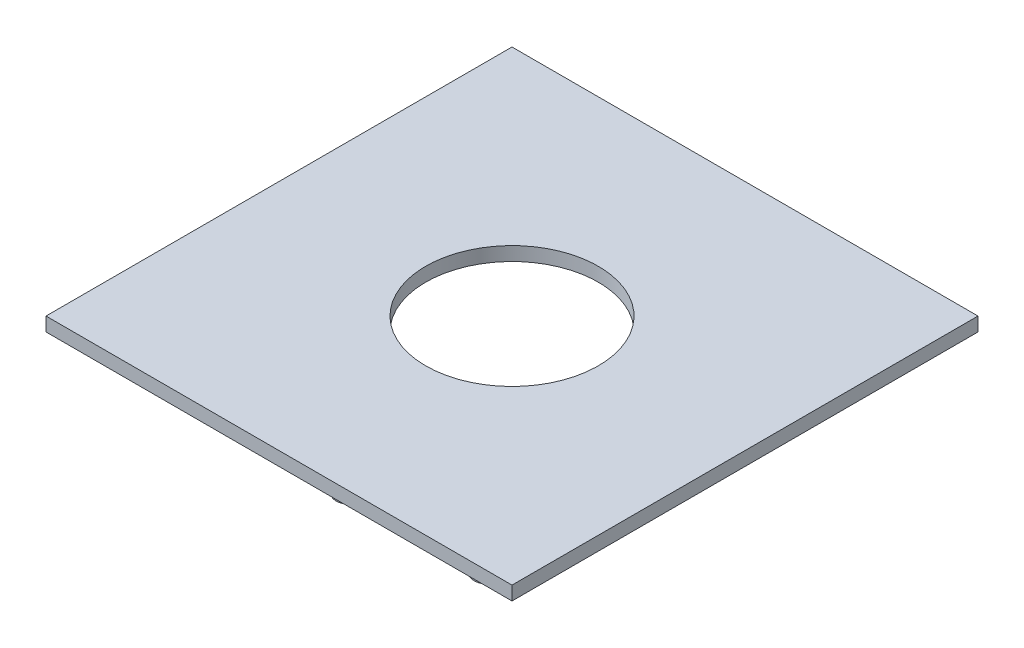
SolidWorks part; units mm, degrees
ref_plane "Front Plane" through (0, 0, 0) normal (0, 0, 1) x (1, 0, 0)
ref_plane "Top Plane" through (0, 0, 0) normal (0, 1, 0) x (1, 0, 0)
ref_plane "Right Plane" through (0, 0, 0) normal (1, 0, 0) x (0, 0, -1)
sketch "Sketch1" plane through (0, 0, 0) normal (0, 1, 0) x (1, 0, 0)
  line L1 (-67.5, 67.5) -> (67.5, 67.5)
  line L2 (-67.5, 67.5) -> (-67.5, -67.5)
  line L3 (-67.5, -67.5) -> (67.5, -67.5)
  line L4 (67.5, 67.5) -> (67.5, -67.5)
  line L5 (-67.5, 67.5) -> (67.5, -67.5) construction
  line L6 (-67.5, -67.5) -> (67.5, 67.5) construction
  line L7 (-67.5, -59.5) -> (67.5, -59.5) construction
  circle A0 centre (12.5, -59.5) radius 3.9
  circle A2 centre (52.5, -59.5) radius 3.9
  point P0 (0, 0)
  dimension "D1" = 7.8
  dimension "D5" = 7.8
  dimension "D2" = 40
  dimension "D3" = 8
  dimension "D4" = 135
  dimension "D6" = 15
  dimension "D7" = 135
extrude "Boss-Extrude1" add sketch "Sketch1" along normal blind 4 contours A0 | A2 | L4 L1 L2 L3 A2 A0 region at (-0.1713, 0, -0.3136) region at (12.5, 0, 59.5) region at (52.5, 0, 59.5)
extrude "Boss-Extrude2" add sketch "Sketch1<3>" against normal blind 4.5 contours A0 | A2
sketch "Sketch1<3>" plane through (0, 0, 0) normal (0, 1, 0) x (1, 0, 0) same geometry as "Sketch1"
sketch "Sketch2" plane through (0, 4, 0) normal (0, 1, 0) x (1, 0, 0)
  line L4 (67.5, -67.5) -> (67.5, 67.5)
  line L5 (67.5, 67.5) -> (-67.5, 67.5)
  line L6 (-67.5, 67.5) -> (-67.5, -67.5)
  line L7 (-67.5, -67.5) -> (67.5, -67.5)
  line L8 (67.5, -67.5) -> (67.5, 67.5)
  line L9 (67.5, 67.5) -> (-67.5, 67.5)
  line L10 (-67.5, 67.5) -> (-67.5, -67.5)
  line L11 (-67.5, -67.5) -> (67.5, -67.5)
  circle A0 centre (0, 0) radius 25
  dimension "D2" = 50
  dimension "D1" = 0
extrude "Cut-Extrude1" cut sketch "Sketch2" against normal blind 10 contours A0 region at (0, 4, 0)
